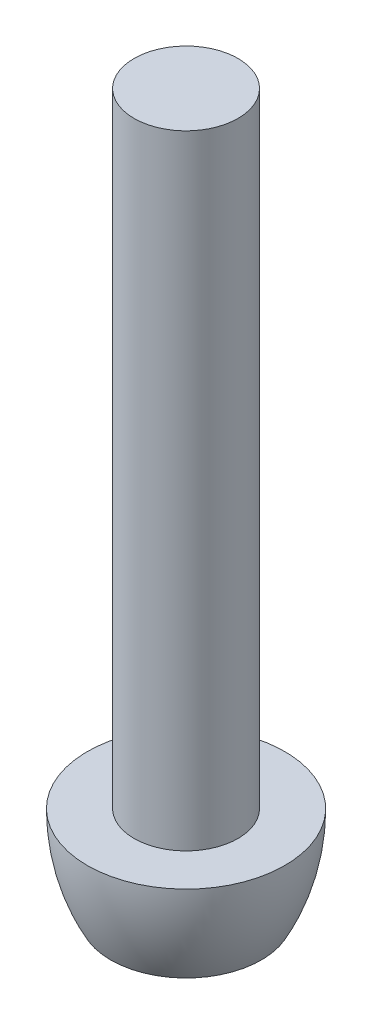
SolidWorks part; units mm, degrees
note: '?' marks a value the reader was unsure of. The reader was unsure of these and kept them because the rebuilt part matched: shared geometry of "草图1<3>".
ref_plane "前视基准面" through (0, 0, 0) normal (0, 0, 1) x (1, 0, 0)
ref_plane "上视基准面" through (0, 0, 0) normal (0, 1, 0) x (1, 0, 0)
ref_plane "右视基准面" through (0, 0, 0) normal (1, 0, 0) x (0, 0, -1)
sketch "草图1" plane through (0, 0, 0) normal (0, 1, 0) x (1, 0, 0)
  line L0 (1, 0) -> (1.9, 0) construction
  circle A0 centre (0, 0) radius 1
  circle A1 centre (0, 0) radius 1.9
  circle A2 centre (0, 0) radius 1.45 construction
  point P7 (1.45, 0)
  dimension "d" = 2
  dimension "D " = 3.8
extrude "公称长度" add sketch "草图1" along normal blind 12 contours A0
cosmetic thread "装饰螺纹线1" parameters "D2"=0.0001
extrude "头部高" add sketch "草图1<3>" against normal blind 1.8 contours A0 | A1 A0
sketch "草图1<3>" plane through (0, 0, 0) normal (0, 1, 0) x (1, 0, 0) same geometry as "草图1"
sketch "草图2" plane through (0, 0, 0) normal (0, 0, 1) x (1, 0, 0)
  line L0 (1.45, 0) -> (-1.45, 0) construction
  line L2 (-1.9, -1.8) -> (1.9, -1.8) construction
  line L6 (1.9, 0) -> (-1.9, 0) construction
  line L7 (-1.9, 0) -> (-1.9, -1.8)
  line L8 (-1.9, -1.8) -> (-1.45, -1.8)
  arc A1 (-1.9, 0) -> (-1.45, -1.8) centre (1.925, 0) ccw
  point P0 (-1.45, 0)
ref_axis "基准轴1" through (0, 12, 0) along (0, -1, 0)?
revolve "切除-旋转1" cut sketch "草图2" angle 360
sketch "草图3" plane through (0, -1.8, 0) normal (0, -1, 0) x (1, 0, 0)
  line L1 (-0.2887, -0.5) -> (0.2887, -0.5)
  line L2 (0.2887, -0.5) -> (0.5774, 0)
  line L3 (0.5774, 0) -> (0.2887, 0.5)
  line L4 (0.2887, 0.5) -> (-0.2887, 0.5)
  line L5 (-0.2887, 0.5) -> (-0.5774, 0)
  line L6 (-0.5774, 0) -> (-0.2887, -0.5)
  circle A0 centre (0, 0) radius 0.5 construction
  dimension "D1" = 1
extrude "切除-拉伸1" cut sketch "草图3" against normal blind 0.6
